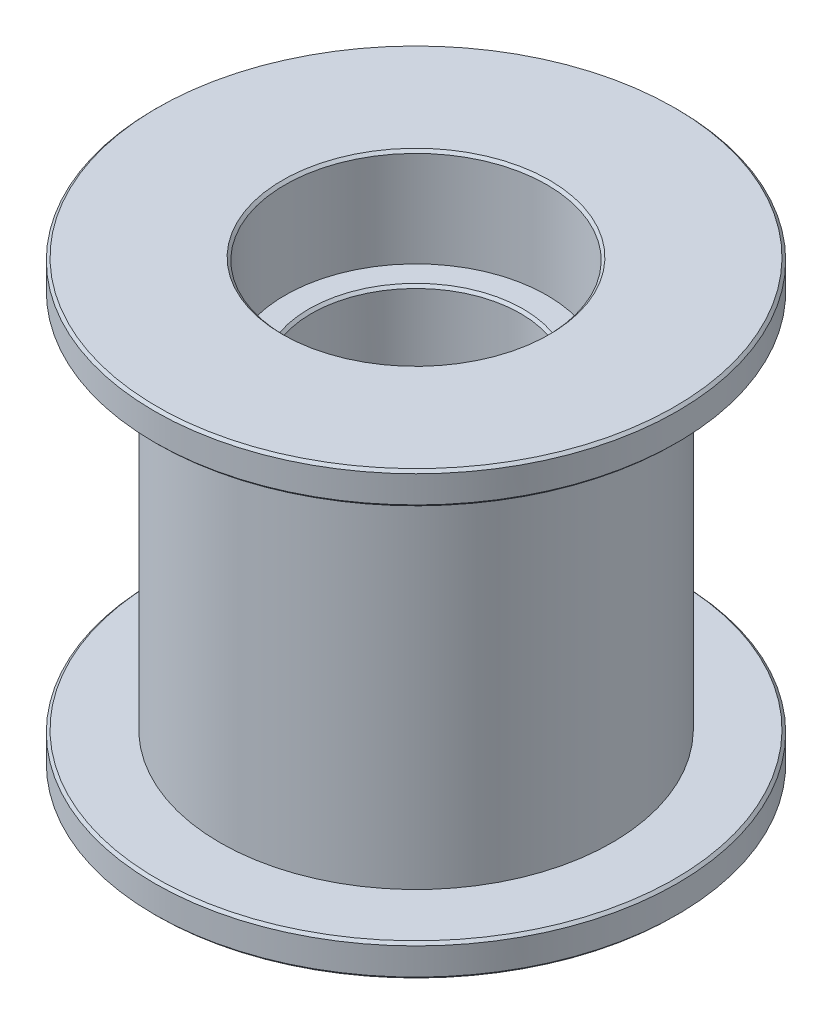
SolidWorks part; units mm, degrees
material "6061-T6 (SS)"
ref_plane "Front Plane" through (0, 0, 0) normal (0, 0, 1) x (1, 0, 0)
ref_plane "Top Plane" through (0, 0, 0) normal (0, 1, 0) x (1, 0, 0)
ref_plane "Right Plane" through (0, 0, 0) normal (1, 0, 0) x (0, 0, -1)
sketch "Sketch1" plane through (0, 0, 0) normal (0, 0, 1) x (1, 0, 0)
  line L0 (6.3627, 0) -> (12.7, 0)
  line L1 (12.7, 0) -> (12.7, 1.5656)
  line L2 (12.7, 1.5656) -> (9.525, 1.5656)
  line L3 (9.525, 1.5656) -> (9.525, 19.8656)
  line L4 (9.525, 19.8656) -> (12.7, 19.8656)
  line L5 (12.7, 19.8656) -> (12.7, 21.4312)
  line L6 (12.7, 21.4312) -> (6.3627, 21.4312)
  line L7 (0, 21.4312) -> (0, 0) construction
  line L8 (6.3627, 0) -> (6.3627, 4.7752)
  line L9 (6.3627, 4.7752) -> (5.08, 4.7752)
  line L10 (5.08, 4.7752) -> (5.08, 16.656)
  line L11 (5.08, 16.656) -> (6.3627, 16.656)
  line L12 (6.3627, 16.656) -> (6.3627, 21.4312)
  line L13 (6.3627, 21.4312) -> (0, 21.4312) construction
  line L14 (0, 0) -> (6.3627, 0) construction
  dimension "D3" = 18.3
  dimension "D4" = 21.4312
  dimension "D1" = 19.05
  dimension "D2" = 25.4
  dimension "D5" = 12.7254
  dimension "D6" = 4.7752
  dimension "D7" = 10.16
revolve "Revolve1" add sketch "Sketch1" angle 360 about L7
chamfer "Chamfer1" distance 0.127 angle 45 8 edges at (0, 19.8656, 12.7) (0, 1.5656, 12.7) (0, 0, 6.3627) (0, 0, 12.7) (0, 16.656, 5.08) (0, 4.7752, 5.08) (0, 21.4312, 12.7) (0, 21.4312, 6.3627)
equation "\"D3@Sketch1\"=18.3mm"
